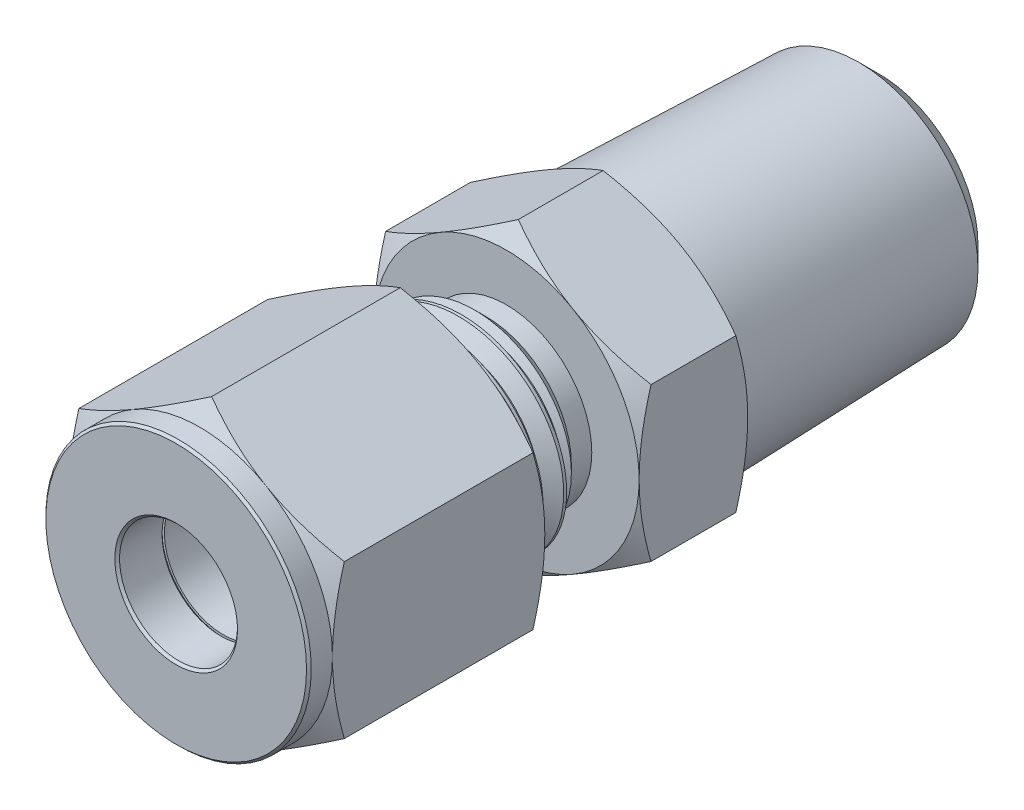
SolidWorks part; units mm, degrees
material "AISI 316 Stainless Steel Sheet (SS)"
ref_plane "Front Plane" through (0, 0, 0) normal (0, 0, 1) x (1, 0, 0)
ref_plane "Top Plane" through (0, 0, 0) normal (0, 1, 0) x (1, 0, 0)
ref_plane "Right Plane" through (0, 0, 0) normal (1, 0, 0) x (0, 0, -1)
sketch "Sketch1" plane through (0, 0, 0) normal (1, 0, 0) x (0, 0, -1)
  line L0 (0, 0) -> (37.846, 0) construction
  line L1 (0, 3.175) -> (0, -3.175) construction
  line L2 (12.7, 7.1437) -> (12.7, -7.1437) construction
  line L3 (5.08, 5.5562) -> (5.08, -5.5562) construction
  line L4 (5.08, 5.5562) -> (5.08, 4.2862) construction
  line L5 (23.622, 7.1437) -> (23.622, -7.1437) construction
  line L6 (4.445, 4.699) -> (9.3218, 3.6068) construction
  line L7 (9.3218, 3.6068) -> (9.3218, 3.175) construction
  line L8 (9.3218, 3.175) -> (5.1308, 3.175) construction
  line L9 (5.1308, 3.175) -> (4.445, 3.8608) construction
  line L10 (4.445, 3.8608) -> (4.445, 4.699) construction
  line L11 (2.54, 4.6609) -> (3.556, 4.6609) construction
  line L12 (3.556, 4.6609) -> (3.556, 3.8608) construction
  line L13 (3.556, 3.8608) -> (4.445, 3.8608) construction
  line L14 (23.622, 2.3749) -> (23.622, -2.3749) construction
  line L15 (4.445, 3.8608) -> (4.445, 3.175) construction
  line L16 (5.1308, 3.175) -> (2.54, 3.175) construction
  line L17 (2.54, 3.175) -> (2.54, 4.6609) construction
  line L18 (4.445, 3.175) -> (5.1308, 3.175) construction
  line L19 (0, 3.175) -> (2.54, 3.175) construction
  line L20 (2.54, 3.175) -> (5.08, 3.175) construction
  line L21 (37.846, 6.3878) -> (37.846, -6.3878) construction
  line L22 (22.7432, 6.858) -> (22.7432, -6.858) construction
  line L23 (22.7432, 6.858) -> (37.846, 6.3878) construction
  line L24 (22.7432, 6.858) -> (22.7432, 5.4469) construction
  line L25 (27.6403, 6.7055) -> (27.6403, -6.7055) construction
  line L26 (37.846, 4.6228) -> (37.846, -4.6228) construction
  point P4 (1.27, 0)
  point P10 (5.08, 0)
  point P12 (12.7, 0)
  point P15 (17.78, 0)
  point P16 (7.366, 0)
  point P17 (15.24, 0)
  point P33 (23.622, 0)
  point P40 (22.7432, 0)
  point P44 (27.6403, 0)
  dimension "R" = 14.224
sketch "Sketch2" plane through (0, 0, 0) normal (0, 0, 1) x (1, 0, 0)
  line L0 (0, 3.175) -> (0, -3.175) construction
  line L1 (0, 8.2489) -> (-7.1437, 4.1244)
  line L2 (-7.1437, 4.1244) -> (-7.1438, -4.1244)
  line L3 (-7.1438, -4.1244) -> (0, -8.2489)
  line L4 (0, -8.2489) -> (7.1437, -4.1244)
  line L5 (7.1437, -4.1244) -> (7.1438, 4.1244)
  line L6 (7.1438, 4.1244) -> (0, 8.2489)
  line L7 (0, 8.2489) -> (0, 0) construction
  circle A0 centre (0, 0) radius 7.1438 construction
extrude "Boss-Extrude1" add sketch "Sketch2" against normal up to vertex (12.7 mm away) up to point (0, 0, -12.7)
sketch "Sketch3" plane through (0, 0, 0) normal (1, 0, 0) x (0, 0, -1)
  line L0 (0, 8.2489) -> (0, 7.1437)
  line L1 (0, 4.1244) -> (0, 8.2489) construction
  line L2 (0, 7.1437) -> (1.27, 7.1437)
  line L3 (1.27, 7.1437) -> (1.9081, 8.2489)
  line L4 (12.7, 8.2489) -> (0, 8.2489) construction
  line L5 (1.9081, 8.2489) -> (12.0619, 8.2489)
  line L6 (12.0619, 8.2489) -> (12.7, 7.1437)
  line L7 (12.7, 7.1437) -> (12.7, 8.2489)
  line L8 (12.7, 8.2489) -> (12.7, 9.354)
  line L9 (12.7, 9.354) -> (0, 9.354)
  line L10 (0, 9.354) -> (0, 8.2489)
  line L11 (0, 3.175) -> (0, 0)
  line L12 (0, 3.175) -> (0, -3.175) construction
  line L13 (0, 0) -> (12.7, 0)
  line L14 (12.7, 7.1437) -> (12.7, -7.1437) construction
  line L15 (12.7, 0) -> (12.7, 5.5562)
  line L16 (12.7, 5.5562) -> (5.08, 5.5562)
  line L17 (5.08, 5.5562) -> (5.08, 4.2862) construction
  line L18 (5.08, 4.2862) -> (2.54, 4.2862) construction
  line L19 (2.54, 4.2862) -> (2.54, 3.175)
  line L20 (2.54, 3.175) -> (0, 3.175)
  line L21 (2.54, 4.2862) -> (2.54, 5.5562) construction
  line L22 (2.54, 5.5562) -> (5.08, 5.5562) construction
  line L23 (5.08, 4.9212) -> (2.54, 4.9213)
  line L24 (2.54, 4.9213) -> (2.54, 4.2862)
  line L25 (5.08, 4.9212) -> (5.08, 5.5562)
  dimension "D1" = 30
  dimension "D2" = 1.27
revolve "Cut-Revolve1" cut sketch "Sketch3" angle 360 about L0
chamfer "Chamfer1" distance 0.127 angle 45 3 edges at (3.175, 0, -2.54) (3.175, 0, 0) (7.1437, 0, 0)
sketch "Sketch4" plane through (0, 0, 0) normal (1, 0, 0) x (0, 0, -1)
  line L1 (23.622, 0) -> (7.366, 0)
  line L2 (23.622, 0) -> (23.622, 5.5563)
  line L3 (23.622, 5.5563) -> (7.366, 5.5562)
  line L4 (7.366, 0) -> (7.366, 5.5562)
  dimension "D1" = 16.256
revolve "Revolve1" add sketch "Sketch4" angle 360 about L1
sketch "Sketch5" plane through (0, 0, -7.366) normal (0, 0, -1) x (-1, 0, 0)
  circle A0 centre (0, 0) radius 5.5562 construction
  circle A1 centre (0, 0) radius 5.5562
  point P3 (0, 5.5562)
curve "Helix/Spiral1" pitch 1.27 height 17.526 radius 5.5562 centre (0, 0, -7.366) axis (0, 0, -1) start towards (0, 1, 0)
sketch "Sketch6" plane through (0, 0, 0) normal (1, 0, 0) x (0, 0, -1)
  line L0 (6.1754, 5.6937) -> (7.4454, 5.6937) construction
  line L1 (7.4454, 5.6937) -> (6.8104, 4.5939) construction
  line L2 (6.8104, 4.5939) -> (6.1754, 5.6937) construction
  line L3 (6.731, 4.7314) -> (6.8898, 4.7314) construction
  line L4 (6.2548, 5.5563) -> (7.366, 5.5563) construction
  line L5 (6.8104, 4.5939) -> (6.8104, 4.7314) construction
  line L6 (6.8104, 5.5563) -> (6.8104, 5.6937) construction
  line L7 (6.731, 4.7314) -> (6.2151, 5.625)
  line L8 (6.2151, 5.625) -> (7.4057, 5.625)
  line L9 (7.4057, 5.625) -> (6.8898, 4.7314)
  line L10 (6.8898, 4.7314) -> (6.731, 4.7314)
  point P10 (6.8104, 5.625)
  dimension "D1" = 1.27
  dimension "D2" = 0.1588
sweep "Cut-Sweep1" cut profiles "Sketch6" path "Helix/Spiral1" align with end faces yes
sketch "Sketch7" plane through (0, 0, -23.622) normal (0, 0, -1) x (-1, 0, 0)
  line L0 (0, 0) -> (0, 8.2489) construction
  line L1 (0, 8.2489) -> (-7.1438, 4.1244)
  line L2 (-7.1438, 4.1244) -> (-7.1438, -4.1244)
  line L3 (-7.1438, -4.1244) -> (0, -8.2489)
  line L4 (0, -8.2489) -> (7.1438, -4.1244)
  line L5 (7.1438, -4.1244) -> (7.1438, 4.1244)
  line L6 (7.1438, 4.1244) -> (0, 8.2489)
  circle A0 centre (0, 0) radius 7.1438 construction
extrude "Boss-Extrude2" add sketch "Sketch7" against normal up to vertex (5.842 mm away) up to point (0, 0, -17.78)
sketch "Sketch8" plane through (0, 0, 0) normal (1, 0, 0) x (0, 0, -1)
  line L0 (7.366, 5.6937) -> (7.366, 4.5939)
  line L1 (7.366, 4.5939) -> (8.4659, 5.6937)
  line L2 (8.4659, 5.6937) -> (7.366, 5.6937)
  line L3 (17.78, 5.6937) -> (15.5803, 5.6937)
  line L4 (15.5803, 5.6937) -> (16.6801, 4.5939)
  line L5 (16.6801, 4.5939) -> (17.78, 4.5939)
  line L6 (17.78, 4.5939) -> (17.78, 5.6937)
  line L7 (17.78, 7.1438) -> (18.4181, 8.2489)
  line L8 (17.78, 8.2489) -> (17.78, 4.1244) construction
  line L9 (17.78, 8.2489) -> (23.622, 8.2489) construction
  line L10 (18.4181, 8.2489) -> (22.9839, 8.2489)
  line L11 (15.24, 2.3749) -> (23.622, 2.3749)
  line L12 (22.9839, 8.2489) -> (23.622, 7.1437)
  line L13 (23.622, -4.1244) -> (23.622, 4.1244) construction
  line L14 (23.622, 8.2489) -> (23.622, 9.354)
  line L15 (23.622, 9.354) -> (17.78, 9.354)
  line L16 (17.78, 9.354) -> (17.78, 8.2489)
  line L17 (17.78, 8.2489) -> (17.78, 7.1438)
  line L18 (6.8104, 4.5939) -> (7.366, 4.5939) construction
  line L19 (7.4454, 5.6937) -> (7.366, 5.6937) construction
  line L20 (8.4659, 5.6937) -> (15.5803, 5.6937) construction
  line L21 (16.6801, 4.5939) -> (7.366, 4.5939) construction
  line L22 (7.366, 4.0448) -> (11.2498, 3.175)
  line L23 (23.622, 7.1437) -> (23.622, 8.2489)
  line L24 (7.366, 3.9289) -> (7.366, -4.7433) construction
  line L25 (4.445, 4.699) -> (9.3218, 3.6068) construction
  line L26 (23.622, 0) -> (7.366, 0)
  line L27 (7.366, 0) -> (7.366, 4.0448)
  line L28 (11.2498, 3.175) -> (15.24, 3.175)
  line L29 (15.24, 3.175) -> (15.24, 2.3749)
  line L30 (23.622, 2.3749) -> (23.622, 0)
  line L31 (15.24, 0) -> (15.24, 2.3749) construction
  line L32 (23.622, 7.1437) -> (23.622, -7.1437) construction
  dimension "D1" = 30
revolve "Cut-Revolve2" cut sketch "Sketch8" angle 360 about L0
sketch "Sketch9" plane through (0, 0, 0) normal (1, 0, 0) x (0, 0, -1)
  line L0 (4.445, 4.699) -> (4.445, 3.8608)
  line L1 (4.445, 3.8608) -> (5.1308, 3.175)
  line L2 (5.1308, 3.175) -> (9.3218, 3.175)
  line L3 (9.3218, 3.175) -> (9.3218, 3.6068)
  line L4 (9.3218, 3.6068) -> (4.445, 4.699)
revolve "Revolve2" add sketch "Sketch9" angle 360 about L0
sketch "Sketch10" plane through (0, 0, 0) normal (1, 0, 0) x (0, 0, -1)
  line L0 (2.54, 4.6609) -> (3.556, 4.6609)
  line L1 (3.556, 4.6609) -> (3.556, 3.8608)
  line L2 (3.556, 3.8608) -> (4.445, 3.8608)
  line L4 (4.445, 3.8608) -> (5.1308, 3.175)
  line L5 (5.1308, 3.175) -> (2.54, 3.175)
  line L6 (2.54, 3.175) -> (2.54, 4.6609)
revolve "Revolve3" add sketch "Sketch10" angle 360 about L0
sketch "Sketch11" plane through (0, 0, 0) normal (1, 0, 0) x (0, 0, -1)
  line L0 (22.7432, 0) -> (37.846, 0)
  line L1 (37.846, 0) -> (37.846, 6.3878)
  line L2 (37.846, 6.3878) -> (22.7432, 6.858)
  line L3 (22.7432, 6.858) -> (22.7432, 0)
revolve "Revolve4" add sketch "Sketch11" angle 360 about L0
sketch "Sketch12" plane through (0, 0, -37.846) normal (0, 0, -1) x (-1, 0, 0)
  circle A1 centre (0, 0) radius 6.3878
  circle A2 centre (0, 0) radius 6.3878
  point P0 (0, 6.3878)
  dimension "D1" = 0
curve "Helix/Spiral2"
sketch "Sketch13" plane through (0, 0, 0) normal (1, 0, 0) x (0, 0, -1)
  line L0 (37.7578, 6.5405) -> (39.1689, 6.5405) construction
  line L1 (37.7578, 6.5405) -> (38.4634, 5.3185) construction
  line L2 (38.4634, 5.3185) -> (39.1689, 6.5405) construction
  line L3 (38.3752, 5.4712) -> (38.5516, 5.4712) construction
  line L4 (37.846, 6.3878) -> (39.0807, 6.3878) construction
  line L5 (38.4634, 5.3185) -> (38.4634, 5.4712) construction
  line L6 (38.4634, 6.3878) -> (38.4634, 6.5405) construction
  line L7 (38.4634, 6.4642) -> (39.1248, 6.4642) construction
  line L8 (38.4634, 5.3185) -> (38.4634, -6.3686) construction
  line L9 (38.4634, -6.3686) -> (37.0529, -6.4125) construction
  line L10 (37.0529, -6.4125) -> (35.6425, -6.4564) construction
  line L11 (35.6425, -6.4564) -> (34.2321, -6.5003) construction
  line L12 (37.7578, 6.5405) -> (39.1248, 6.4642)
  line L13 (39.1248, 6.4642) -> (38.5516, 5.4712)
  line L14 (38.5516, 5.4712) -> (38.3752, 5.4712)
  line L15 (38.3752, 5.4712) -> (37.7578, 6.5405)
  line L16 (22.7432, -6.858) -> (37.846, -6.3878) construction
  line L17 (34.2321, -6.5003) -> (32.8217, -6.5442) construction
  line L18 (32.8217, -6.5442) -> (31.4112, -6.5881) construction
  dimension "D1" = 1.4111
  dimension "D2" = 0.1764
sweep "Cut-Sweep2" [suppressed] cut profiles "Sketch13" path "Helix/Spiral2"
combine bodies "Combine1" operation type add bodies to combine 113 121
sketch "Sketch14" plane through (0, 0, 0) normal (1, 0, 0) x (0, 0, -1)
  line L0 (38.4634, 5.3185) -> (37.846, 5.3185) construction
  line L5 (37.846, 6.3878) -> (37.846, -6.3878) construction
  line L6 (37.846, 5.3185) -> (36.6239, 6.5405)
  line L7 (36.6239, 6.5405) -> (37.846, 6.5405)
  line L8 (37.846, 6.5405) -> (37.846, 5.3185)
  line L9 (37.7578, 6.5405) -> (39.1689, 6.5405) construction
  line L10 (37.846, 4.6228) -> (22.7432, 4.6228)
  line L11 (22.7432, 4.6228) -> (22.7432, 0) construction
  line L12 (19.9655, 0) -> (37.846, 0)
  line L13 (19.9655, 0) -> (22.7432, 4.6228)
  line L14 (37.846, 0) -> (37.846, 4.6228)
  dimension "D1" = 59
revolve "Cut-Revolve4" cut sketch "Sketch14" angle 360 about L0
equation "\"D4@Helix/Spiral1\" = \"Straight Thread Pitch@Sketch1\""
equation "\"D3@Helix/Spiral1\" = \"D4@Helix/Spiral1\" + \"D1@Sketch4\""
equation "\"D1@Sketch6\" = \"D4@Helix/Spiral1\""
equation "\"D2@Sketch6\" = \"D1@Sketch6\" / 8"
equation "\"D4@Helix/Spiral2\" = \"Pipe Pitch@Sketch1\""
equation "\"D3@Helix/Spiral2\" = \"D4@Helix/Spiral2\" + \"L4@Sketch1\""
equation "\"D1@Sketch13\" = \"D4@Helix/Spiral2\""
equation "\"D2@Sketch13\" = \"D1@Sketch13\" / 8"
